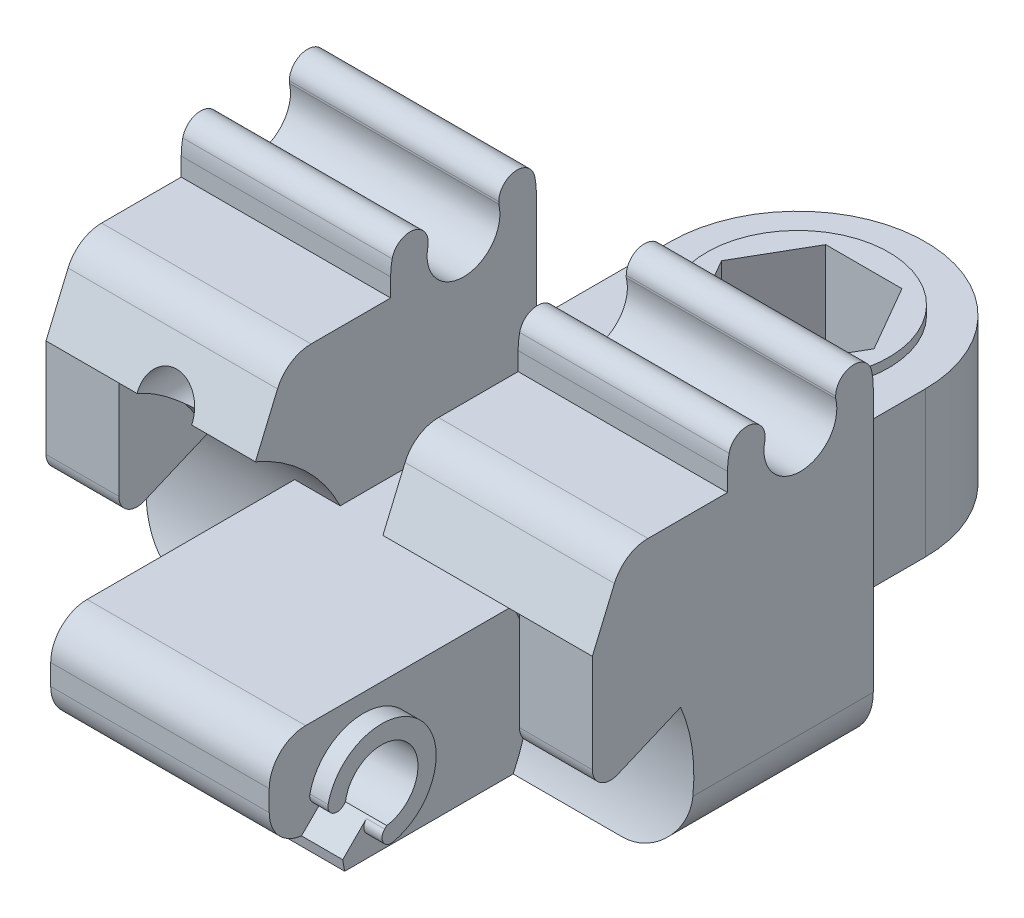
SolidWorks part; units mm, degrees
ref_plane "Front Plane" through (0, 0, 0) normal (0, 0, 1) x (1, 0, 0)
ref_plane "Top Plane" through (0, 0, 0) normal (0, 1, 0) x (1, 0, 0)
ref_plane "Right Plane" through (0, 0, 0) normal (1, 0, 0) x (0, 0, -1)
sketch "Sketch3" plane through (0, 0, 0) normal (1, 0, 0) x (0, 0, -1)
  line L0 (0.2828, -1.9799) -> (-1.9799, 0.2828)
  line L1 (0.2828, -1.9799) -> (-1.1314, -3.3941)
  line L2 (-1.1314, -3.3941) -> (-0.8188, -5.1668)
  line L3 (-0.8188, -5.1668) -> (-3.9199, -8.2678)
  line L4 (-1.9799, 0.2828) -> (-3.3941, -1.1314)
  line L5 (-3.3941, -1.1314) -> (-5.1668, -0.8188)
  line L6 (-5.1668, -0.8188) -> (-8.2678, -3.9199)
  line L7 (-0.8485, -0.8485) -> (0, 0) construction
  line L8 (0, 0) -> (-2, 0) construction
  line L9 (-1.9799, 0.2828) -> (-5.1668, -0.8188) construction
  line L10 (-0.8188, -5.1668) -> (0.2828, -1.9799) construction
  circle A0 centre (0, 0) radius 2
  circle A1 centre (0, 0) radius 8.65 construction
  circle A2 centre (0, 0) radius 9.15 construction
  circle A3 centre (0, 0) radius 9.15
  dimension "D1" = 4
  dimension "D2" = 17.3
  dimension "D4" = 0.5
  dimension "D5" = 2
  dimension "D7" = 3.2
  dimension "D6" = 1.8
  dimension "D8" = 45
  dimension "D9" = 125
extrude "Boss-Extrude1" add sketch "Sketch3" along normal mid plane 12 contours A3 L6 L5 L4 A0 L1 L2 L3 | A3 region at (0, -1.48, -1.7064)
sketch "Sketch5" plane through (0, 0, 0) normal (1, 0, 0) x (0, 0, -1)
  line L0 (0, 9.15) -> (29.856, 9.15)
  line L1 (29.856, 9.15) -> (29.856, -9.15)
  line L2 (29.856, -9.15) -> (0, -9.15)
  arc A0 (-3.9199, -8.2678) -> (-8.2678, -3.9199) centre (0, 0) ccw construction
  arc A1 (0, -9.15) -> (0, 9.15) centre (0, 0) ccw
  dimension "D1" = 29.856
extrude "Boss-Extrude2" add sketch "Sketch5" along normal mid plane 14
sketch "Sketch6" plane through (0, 9.15, 0) normal (0, 1, 0) x (1, 0, 0)
  line L0 (7, 29.856) -> (-7, 29.856) construction
  circle A0 centre (0, 29.856) radius 7
extrude "Boss-Extrude3" add sketch "Sketch6" against normal up to surface (18.3 mm away) up to face at (0, -9.15, -9.952)
sketch "Sketch7" plane through (0, 0, 0) normal (0, 1, 0) x (1, 0, 0)
  circle A0 centre (0, 29.856) radius 4.5
  dimension "D1" = 9
extrude "Boss-Extrude4" add sketch "Sketch7" along normal blind 8 and the other way blind 8
sketch "Sketch8" plane through (0, 9.15, 0) normal (0, 1, 0) x (1, 0, 0)
  line L0 (6, -9.15) -> (6, 0) construction
  line L1 (-6, 0) -> (-6, -9.15) construction
  line L3 (7, 0) -> (7, 29.856) construction
  line L4 (-7, 29.856) -> (-7, 0) construction
  line L5 (-7, 0) -> (-6, 0) construction
  line L6 (6, 0) -> (7, 0) construction
  line L7 (6, -9.15) -> (6, 0)
  line L8 (-6, 0) -> (-6, -9.15)
  line L9 (-6, -9.15) -> (6, -9.15)
  line L10 (7, 0) -> (7, 29.856)
  line L11 (-7, 29.856) -> (-7, 0)
  line L12 (-7, 0) -> (-6, 0)
  line L13 (6, 0) -> (7, 0)
  arc A0 (7, 29.856) -> (-7, 29.856) centre (0, 29.856) ccw construction
  arc A1 (7, 29.856) -> (-7, 29.856) centre (0, 29.856) ccw
  line M10 (7, 0) -> (7, 29.856)
  arc M11 (7, 29.856) -> (-7, 29.856) centre (0, 29.856) ccw
  line M12 (-7, 29.856) -> (-7, 0)
  line M13 (-7, 0) -> (-6, 0)
  line M14 (-6, 0) -> (6, 0)
  line M15 (6, 0) -> (7, 0)
extrude "Cut-Extrude2" cut sketch "Sketch8" against normal offset from surface (5.15 mm away) 4 contours M15 M10 M11 M12 M13 M14 | L8 L9 L7 M14 region at (0, 9.15, 4.575) region at (0, 9.15, -17.7114) up to plane "Top Plane"
sketch "Sketch9" plane through (0, -9.15, 0) normal (0, -1, 0) x (1, 0, 0)
  line L7 (6, 0) -> (6, 9.15)
  line L8 (7, 0) -> (6, 0)
  line L9 (7, -29.856) -> (7, 0)
  line L10 (-7, 0) -> (-7, -29.856)
  line L11 (-6, 0) -> (-7, 0)
  line L12 (-6, 9.15) -> (-6, 0)
  line L13 (6, 9.15) -> (-6, 9.15)
  line L14 (6, 0) -> (6, 9.15)
  line L15 (7, 0) -> (6, 0)
  line L16 (7, -29.856) -> (7, 0)
  line L17 (-7, 0) -> (-7, -29.856)
  line L18 (-6, 0) -> (-7, 0)
  line L19 (-6, 9.15) -> (-6, 0)
  line L20 (6, 9.15) -> (-6, 9.15)
  arc A1 (-7, -29.856) -> (7, -29.856) centre (0, -29.856) ccw
  arc A2 (-7, -29.856) -> (7, -29.856) centre (0, -29.856) ccw
  line M10 (-7, 0) -> (-7, -29.856)
  arc M11 (-7, -29.856) -> (7, -29.856) centre (0, -29.856) ccw
  line M12 (7, -29.856) -> (7, 0)
  line M13 (7, 0) -> (6, 0)
  line M14 (6, 0) -> (-6, 0)
  line M15 (-6, 0) -> (-7, 0)
  dimension "D1" = 0
extrude "Cut-Extrude4" cut sketch "Sketch9" against normal offset from surface (5.15 mm away) 4 contours M15 M10 M11 M12 M13 M14 | L14 L20 L19 M14 region at (0, -9.15, 4.575) region at (0, -9.15, -17.7114) up to plane "Top Plane"
sketch "Sketch24" plane through (-6, 0, 0) normal (-1, 0, 0) x (0, 0, 1)
  line L0 (1.9799, 0.2828) -> (2.9258, -0.6631)
  line L1 (1.9799, 0.2828) -> (3.3941, -1.1314) construction
  line L2 (-0.2828, -1.9799) -> (0.6631, -2.9258)
  line L3 (-0.2828, -1.9799) -> (1.1314, -3.3941) construction
  arc A0 (1.9799, 0.2828) -> (-0.2828, -1.9799) centre (0, 0) ccw construction
  arc A1 (1.9799, 0.2828) -> (-0.2828, -1.9799) centre (0, 0) ccw
  circle A2 centre (0, 0) radius 3
  line M5 (1.1314, -3.3941) -> (-0.2828, -1.9799)
  arc M6 (-0.2828, -1.9799) -> (1.9799, 0.2828) centre (0, 0) cw
  line M7 (1.9799, 0.2828) -> (3.3941, -1.1314)
  dimension "D1" = 6
extrude "Boss-Extrude6" add sketch "Sketch24" along normal blind 1 contours A2 M7 M5 M6 region at (-6, 1.4742, -1.4742)
fillet "Fillet3" radius 0.5 2 edges at (-6.5, -2.9258, 0.6631) (-6.5, -0.6631, 2.9258)
mirror "Mirror1" about plane through (0, 0, 0) normal (1, 0, 0) of "Fillet3", "Boss-Extrude6"
sketch "Sketch10" plane through (0, 0, 0) normal (1, 0, 0) x (0, 0, -1)
  line L3 (8.2294, -4) -> (29.856, -4)
  line L4 (29.856, -4) -> (29.856, 4)
  line L5 (29.856, 4) -> (8.2294, 4)
  line L10 (11, 12.5) -> (11, 17.5) construction
  line L11 (11, 17.5) -> (19, 17.5) construction
  line L12 (19, 17.5) -> (19, 4) construction
  line L13 (5.3059, 12.5) -> (11, 12.5)
  line L14 (0, 0) -> (3.5752, 8.4226) construction
  line L15 (3.5752, 8.4226) -> (5.3059, 12.5)
  line L16 (29.856, 4) -> (8.2294, 4) construction
  line L17 (19, 4) -> (8.2294, 4)
  line L18 (11, 13.5) -> (19, 13.5) construction
  line L19 (29, 14) -> (29, 4) construction
  line L20 (29.856, -4) -> (8.2294, -4) construction
  line L21 (13.0635, 14) -> (16.9365, 14) construction
  line L22 (16.9365, 14) -> (16.9365, 17)
  line L23 (13.0635, 17) -> (13.0635, 14)
  line L24 (11, 13.5) -> (11, 12.5)
  line L25 (19, 13.5) -> (19, 4)
  line L26 (19, -4) -> (8.2294, -4)
  line L27 (19, 4) -> (19, -4)
  arc A0 (13.0635, 14) -> (16.9365, 14) centre (15, 13.5) ccw
  arc A1 (8.2294, -4) -> (8.2294, 4) centre (0, 0) ccw
  arc A2 (8.2294, 4) -> (3.5752, 8.4226) centre (0, 0) ccw
  arc A3 (19, 13.5) -> (16.9365, 17) centre (15, 13.5) ccw
  arc A4 (13.0635, 17) -> (11, 13.5) centre (15, 13.5) ccw
  arc A5 (8.2294, -4) -> (8.2294, 4) centre (0, 0) ccw construction
  arc A6 (8.2294, -4) -> (8.2294, 4) centre (0, 0) ccw
  dimension "D8" = 4
  dimension "D9" = 2
  dimension "D10" = 2.5
  dimension "D2" = 67
  dimension "D3" = 10
  dimension "D4" = 13.5
  dimension "D5" = 5
  dimension "D6" = 15
  dimension "D7" = 5
  dimension "D1" = 0
extrude "Boss-Extrude5" add sketch "Sketch10" along normal mid plane 30 contours A6 L26 L27 L17 | L23 A4 L24 L13 L15 A2 L17 L25 A3 L22 A0 region at (0, 0, -13.9211) region at (0, 9.0484, -12.4398)
ref_plane "Plane1" through (6, 0, 0) normal (1, 0, 0) x (0, 0, -1)
ref_plane "Plane2" through (-6, 0, 0) normal (1, 0, 0) x (0, 0, -1)
sketch "Sketch13" plane through (-6, 0, 0) normal (1, 0, 0) x (0, 0, -1)
  line L0 (0, 5) -> (36.856, 5)
  line L2 (36.856, 4) -> (36.856, 5) construction
  circle A0 centre (0, 0) radius 5 construction
  dimension "D1" = 10
ref_plane "Plane3" through (0, 0, 0) normal (0, 0, 1) x (1, 0, 0)
ref_plane "Plane4" [suppressed] through (0, 0, -32.856) normal (0, 0, -1) x (-1, 0, 0)
ref_plane "Plane5" [suppressed] through (-3, 0, 0) normal (-1, 0, 0) x (0, 0, 1)
sketch "Sketch18" [suppressed] plane through (0, 0, -32.856) normal (0, 0, -1) x (-1, 0, 0)
  line L0 (0, 29) -> (0, 16) construction
  line L2 (3, 29) -> (-3, 29) construction
  circle A0 centre (0, 16) radius 1.9
  dimension "D2" = 3.8
  dimension "D1" = 13
extrude "Cut-Extrude5" [suppressed] cut sketch "Sketch18" against normal blind 1
sketch "Sketch20" plane through (0, 4, 0) normal (0, 1, 0) x (1, 0, 0)
  line L0 (0, 25.356) -> (0, 0) construction
  line L2 (-3.5, -19) -> (3.5, -19)
  line L3 (-3.5, -19) -> (-3.5, 19)
  line L4 (-3.5, 19) -> (3.5, 19)
  line L5 (3.5, -19) -> (3.5, 19)
  line L6 (-3.5, -19) -> (3.5, 19) construction
  line L7 (-3.5, 19) -> (3.5, -19) construction
  line L8 (-7, 19) -> (7, 19) construction
  dimension "D1" = 7
extrude "Cut-Extrude7" cut sketch "Sketch20" along normal through all
sketch "Sketch32" plane through (6, 0, 0) normal (1, 0, 0) x (0, 0, -1)
  line L0 (-5.1668, -0.8188) -> (-5.1668, 4)
  line L1 (8.2294, 4) -> (-8.2294, 4) construction
  line L9 (-3.3941, -1.1314) -> (-2.0905, 0.1722)
  line L10 (0.1722, -2.0905) -> (-1.1314, -3.3941)
  line L11 (-1.1314, -3.3941) -> (-1.0245, -4)
  line L12 (-1.0245, -4) -> (8.2294, -4)
  line L13 (8.2294, 4) -> (-8.2294, 4)
  line L14 (-8.2678, -3.9199) -> (-5.1668, -0.8188)
  line L15 (-5.1668, -0.8188) -> (-3.3941, -1.1314)
  line L16 (-3.3941, -1.1314) -> (-2.0905, 0.1722)
  line L17 (0.1722, -2.0905) -> (-1.1314, -3.3941)
  line L18 (-1.1314, -3.3941) -> (-1.0245, -4)
  line L19 (-1.0245, -4) -> (8.2294, -4)
  line L20 (8.2294, 4) -> (-8.2294, 4)
  line L21 (-8.2678, -3.9199) -> (-5.1668, -0.8188)
  line L22 (-5.1668, -0.8188) -> (-3.3941, -1.1314)
  arc A5 (-2.9329, 0.6309) -> (-2.0905, 0.1722) centre (-2.4441, 0.5258) ccw
  arc A6 (0.6309, -2.9329) -> (-2.9329, 0.6309) centre (0, 0) ccw
  arc A7 (0.1722, -2.0905) -> (0.6309, -2.9329) centre (0.5258, -2.4441) ccw
  arc A8 (8.2294, -4) -> (8.2294, 4) centre (0, 0) ccw
  arc A9 (-8.2294, 4) -> (-8.2678, -3.9199) centre (0, 0) ccw
  arc A10 (-2.9329, 0.6309) -> (-2.0905, 0.1722) centre (-2.4441, 0.5258) ccw
  arc A11 (0.6309, -2.9329) -> (-2.9329, 0.6309) centre (0, 0) ccw
  arc A12 (0.1722, -2.0905) -> (0.6309, -2.9329) centre (0.5258, -2.4441) ccw
  arc A13 (8.2294, -4) -> (8.2294, 4) centre (0, 0) ccw
  arc A14 (-8.2294, 4) -> (-8.2678, -3.9199) centre (0, 0) ccw
  line M21 (8.2294, 4) -> (-8.2294, 4)
  arc M22 (-8.2294, 4) -> (-8.2678, -3.9199) centre (0, 0) ccw
  line M23 (-8.2678, -3.9199) -> (-5.1668, -0.8188)
  dimension "D1" = 0
extrude "Cut-Extrude9" cut sketch "Sketch32" against normal blind 25 contours L0 M23 M21 M22 region at (6, 0.6087, 7.1825)
fillet "Fillet1" radius 2 2 edges at (0, 4, 5.1668) (0, -0.8188, 5.1668)
fillet "Fillet2" radius 1 4 edges at (-9.25, 17, -16.9365) (-9.25, 17, -13.0635) (9.25, 17, -13.0635) (9.25, 17, -16.9365)
sketch "Sketch23" plane through (0, 4, 0) normal (0, 1, 0) x (1, 0, 0)
  line L0 (-7, 29.856) -> (7, 29.856) construction
  line L1 (4.1881, 29.856) -> (2.094, 33.483)
  line L2 (2.094, 33.483) -> (-2.094, 33.483)
  line L3 (-2.094, 33.483) -> (-4.1881, 29.856)
  line L4 (-4.1881, 29.856) -> (-2.094, 26.229)
  line L5 (-2.094, 26.229) -> (2.094, 26.229)
  line L6 (2.094, 26.229) -> (4.1881, 29.856)
  line L7 (-7, 19) -> (-7, 29.856) construction
  circle A0 centre (0, 29.856) radius 3.627 construction
  dimension "D1" = 7.254
extrude "Cut-Extrude8" cut sketch "Sketch23" against normal through all
sketch "Sketch25" plane through (15, 0, 0) normal (1, 0, 0) x (0, 0, -1)
  line L0 (13.0635, 13) -> (16.9365, 13)
  arc A0 (13.0635, 14) -> (16.9365, 14) centre (15, 13.5) ccw construction
  arc A1 (13.0635, 14) -> (16.9365, 14) centre (15, 13.5) ccw
  arc M14 (16.9365, 14) -> (13.0635, 14) centre (15, 13.5) cw
  dimension "D1" = 1.5
extrude "Boss-Extrude7" [suppressed] add sketch "Sketch25" against normal blind 1 contours L0 M14
fillet "Fillet4" [suppressed] radius 0.5
mirror "Mirror2" [suppressed] about plane through (0, 0, 0) normal (1, 0, 0)
fillet "Fillet5" radius 3 2 edges at (15, -4, -13.6147) (-15, -4, -13.6147)
fillet "Fillet7" radius 2 2 edges at (-9.25, 12.5, -5.3059) (9.25, 12.5, -5.3059)
ref_plane "Plane6" through (-8.5, 0, 0) normal (-1, 0, 0) x (0, 0, 1)
sketch "Sketch27" plane through (-8.5, 0, 0) normal (-1, 0, 0) x (0, 0, 1)
  line L0 (0, 8.5) -> (-25.4214, 8.5)
  circle A0 centre (0, 0) radius 8.5 construction
  dimension "D1" = 17
sweep "Cut-Sweep1" cut path "Sketch27" circular profile diameter 3 parameters "D3"=3
sketch "Sketch28" plane through (15, 0, 0) normal (1, 0, 0) x (0, 0, -1)
  line L0 (0, 0) -> (8.4226, 3.5752) construction
  line L1 (8.4226, 3.5752) -> (3.5752, 1.5176)
  line L2 (0, 0) -> (0, 8.2854) construction
  line L3 (3.5752, 1.5176) -> (3.5752, 8.4226)
  arc A0 (9.0952, -1) -> (3.5752, 8.4226) centre (0, 0) ccw construction
  arc A1 (9.0952, -1) -> (3.5752, 8.4226) centre (0, 0) ccw
  arc M6 (3.5752, 8.4226) -> (9.0952, -1) centre (0, 0) cw
  dimension "D1" = 67
extrude "Boss-Extrude8" add sketch "Sketch28" against normal blind 4 contours L3 L1 M6 region at (15, 4.7658, -5.3454)
fillet "Fillet8" radius 1 1 edges at (13, 1.5176, -3.5752)
mirror "Mirror3" about plane through (0, 0, 0) normal (1, 0, 0) of "Fillet8", "Boss-Extrude8"
sketch "Sketch33" plane through (0, 4, 0) normal (0, 1, 0) x (1, 0, 0)
  line L0 (4.1881, 29.856) -> (2.094, 33.483) construction
  line L1 (2.094, 26.229) -> (4.1881, 29.856) construction
  line L2 (-2.094, 26.229) -> (2.094, 26.229) construction
  line L3 (-4.1881, 29.856) -> (-2.094, 26.229) construction
  line L4 (-2.094, 33.483) -> (-4.1881, 29.856) construction
  line L5 (2.094, 33.483) -> (-2.094, 33.483) construction
  line L6 (4.1881, 29.856) -> (2.094, 33.483)
  line L7 (2.094, 26.229) -> (4.1881, 29.856)
  line L8 (-2.094, 26.229) -> (2.094, 26.229)
  line L9 (-4.1881, 29.856) -> (-2.094, 26.229)
  line L10 (-2.094, 33.483) -> (-4.1881, 29.856)
  line L11 (2.094, 33.483) -> (-2.094, 33.483)
  arc A0 (7, 29.856) -> (-7, 29.856) centre (0, 29.856) ccw construction
  arc A1 (7, 29.856) -> (-7, 29.856) centre (0, 29.856) ccw
  circle A2 centre (0, 29.856) radius 5
  line M8 (4.1881, 29.856) -> (2.094, 26.229)
  line M9 (2.094, 26.229) -> (-2.094, 26.229)
  line M10 (-2.094, 26.229) -> (-4.1881, 29.856)
  line M11 (-4.1881, 29.856) -> (-2.094, 33.483)
  line M12 (-2.094, 33.483) -> (2.094, 33.483)
  line M13 (2.094, 33.483) -> (4.1881, 29.856)
  dimension "D1" = 10
extrude "Boss-Extrude9" add sketch "Sketch33" along normal blind 0.5 contours A2 M13 M8 M9 M10 M11 M12 region at (-4.8586, 4, -29.856)
ref_plane "Plane7" through (0, 0, 0) normal (0, -1, 0) x (-1, 0, 0)
